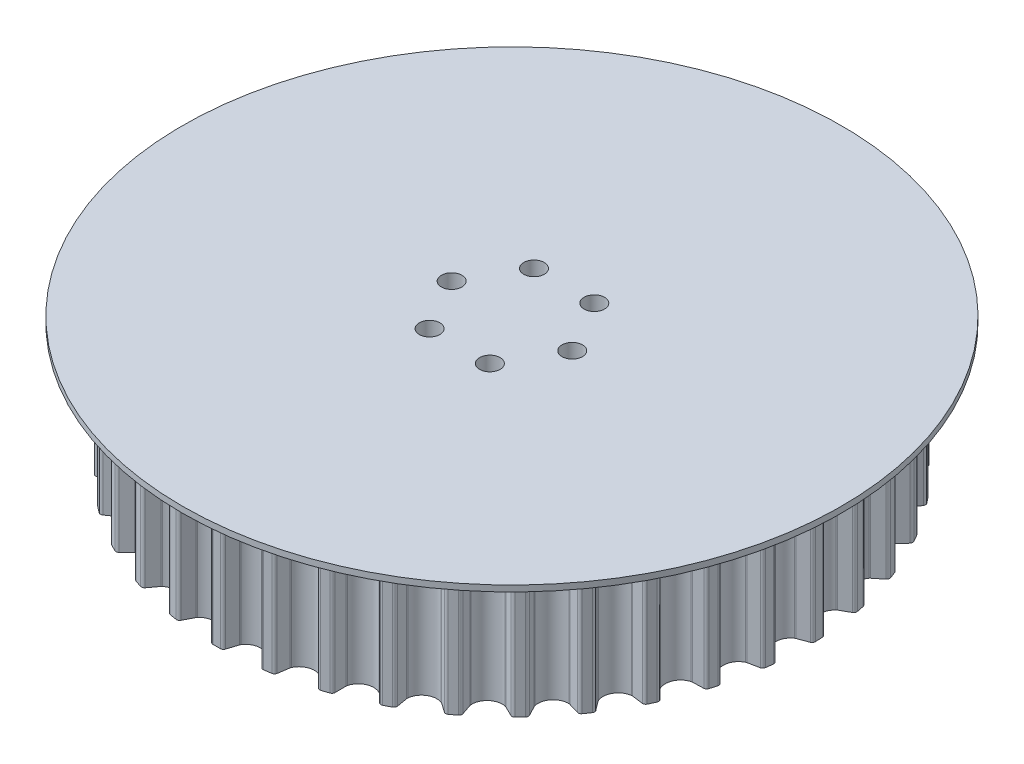
SolidWorks part; units mm, degrees
material "PETG"
ref_plane "Front Plane" through (0, 0, 0) normal (0, 0, 1) x (1, 0, 0)
ref_plane "Top Plane" through (0, 0, 0) normal (0, 1, 0) x (1, 0, 0)
ref_plane "Right Plane" through (0, 0, 0) normal (1, 0, 0) x (0, 0, -1)
sketch "Sketch7" plane through (0, 0, 0) normal (0, 1, 0) x (1, 0, 0)
  line L0 (0, 0) -> (0, 50000) construction
  line L1 (2.1092, 46.8388) -> (2.822, 48.5459)
  line L2 (0, 0) -> (3.9957, 49.4953) construction
  line L3 (0, 0) -> (-3.9957, 49.4953) construction
  line L4 (-2.1092, 46.8388) -> (-2.822, 48.5459)
  line L5 (9.5953, 45.8939) -> (10.5728, 47.4645)
  line L6 (5.4316, 46.5706) -> (5.0018, 48.3699)
  line L7 (16.833, 43.7604) -> (18.0497, 45.1539)
  line L8 (12.8317, 45.0962) -> (12.6961, 46.9412)
  line L9 (23.6346, 40.4935) -> (25.0591, 41.6738)
  line L10 (19.8995, 42.4539) -> (20.0616, 44.2967)
  line L11 (29.8242, 36.1779) -> (31.4196, 37.1143)
  line L12 (26.4519, 38.712) -> (26.9075, 40.5049)
  line L13 (35.2413, 30.9252) -> (36.9663, 31.5937)
  line L14 (32.3192, 33.9675) -> (33.0565, 35.6641)
  line L15 (39.7457, 24.8716) -> (41.5555, 25.2547)
  line L16 (37.3494, 28.3433) -> (38.3494, 29.8997)
  line L17 (43.2207, 18.1739) -> (45.0685, 18.2617)
  line L18 (41.4123, 21.985) -> (42.649, 23.3608)
  line L19 (45.5763, 11.0055) -> (47.4143, 10.7957)
  line L20 (44.4027, 15.0573) -> (45.844, 16.2169)
  line L21 (46.7515, 3.552) -> (48.5321, 3.0501)
  line L22 (46.243, 7.7396) -> (47.8518, 8.653)
  line L23 (46.7159, -3.9935) -> (48.3929, -4.7745)
  line L24 (46.8857, 0.2215) -> (48.6201, 0.865)
  line L25 (45.4703, -11.4355) -> (47.0003, -12.4754)
  line L26 (46.3141, -7.3024) -> (48.1293, -6.9454)
  line L27 (43.0471, -18.5814) -> (44.3905, -19.8532)
  line L28 (44.5429, -14.6371) -> (46.3919, -14.576)
  line L29 (39.509, -25.246) -> (40.6309, -26.7169)
  line L30 (41.6182, -21.5928) -> (43.4529, -21.829)
  line L31 (34.9476, -31.2567) -> (35.8191, -32.8885)
  line L32 (37.6155, -27.9892) -> (39.3886, -28.5167)
  line L33 (29.4811, -36.458) -> (30.0796, -38.2084)
  line L34 (32.6386, -33.6607) -> (34.3042, -34.4658)
  line L35 (23.2511, -40.7149) -> (23.561, -42.5387)
  line L36 (26.8164, -38.4604) -> (28.3312, -39.5222)
  line L37 (16.4188, -43.9174) -> (16.4322, -45.7673)
  line L38 (20.2996, -42.264) -> (21.6245, -43.5551)
  line L39 (9.1614, -45.9825) -> (8.8778, -47.8106)
  line L40 (13.2571, -44.973) -> (14.3578, -46.4599)
  line L41 (1.6666, -46.8566) -> (1.0935, -48.6155)
  line L42 (5.8713, -46.5172) -> (6.7192, -48.1614)
  line L43 (-5.8713, -46.5172) -> (-6.7192, -48.1614)
  line L44 (-1.6666, -46.8566) -> (-1.0935, -48.6155)
  line L45 (-13.2571, -44.973) -> (-14.3578, -46.4599)
  line L46 (-9.1614, -45.9825) -> (-8.8778, -47.8106)
  line L47 (-20.2996, -42.264) -> (-21.6245, -43.5551)
  line L48 (-16.4188, -43.9174) -> (-16.4322, -45.7673)
  line L49 (-26.8164, -38.4604) -> (-28.3312, -39.5222)
  line L50 (-23.2511, -40.7149) -> (-23.561, -42.5387)
  line L51 (-32.6386, -33.6607) -> (-34.3042, -34.4658)
  line L52 (-29.4811, -36.458) -> (-30.0796, -38.2084)
  line L53 (-37.6155, -27.9892) -> (-39.3886, -28.5167)
  line L54 (-34.9476, -31.2567) -> (-35.8191, -32.8885)
  line L55 (-41.6182, -21.5928) -> (-43.4529, -21.829)
  line L56 (-39.509, -25.246) -> (-40.6309, -26.7169)
  line L57 (-44.5429, -14.6371) -> (-46.3919, -14.576)
  line L58 (-43.0471, -18.5814) -> (-44.3905, -19.8532)
  line L59 (-46.3141, -7.3024) -> (-48.1293, -6.9454)
  line L60 (-45.4703, -11.4355) -> (-47.0003, -12.4754)
  line L61 (-46.8857, 0.2215) -> (-48.6201, 0.865)
  line L62 (-46.7159, -3.9935) -> (-48.3929, -4.7745)
  line L63 (0, 0) -> (2.0086, 46.666) construction
  line L64 (-46.243, 7.7396) -> (-47.8518, 8.653)
  line L65 (-46.7515, 3.552) -> (-48.5321, 3.0501)
  line L66 (-44.4027, 15.0573) -> (-45.844, 16.2169)
  line L67 (-45.5763, 11.0055) -> (-47.4143, 10.7957)
  line L68 (-41.4123, 21.985) -> (-42.649, 23.3608)
  line L69 (-43.2207, 18.1739) -> (-45.0685, 18.2617)
  line L70 (-37.3494, 28.3433) -> (-38.3494, 29.8997)
  line L71 (-39.7457, 24.8716) -> (-41.5555, 25.2547)
  line L72 (-32.3192, 33.9675) -> (-33.0565, 35.6641)
  line L73 (-35.2413, 30.9252) -> (-36.9663, 31.5937)
  line L74 (-26.4519, 38.712) -> (-26.9075, 40.5049)
  line L75 (-29.8242, 36.1779) -> (-31.4196, 37.1143)
  line L76 (-19.8995, 42.4539) -> (-20.0616, 44.2967)
  line L77 (-23.6346, 40.4935) -> (-25.0591, 41.6738)
  line L78 (-12.8317, 45.0962) -> (-12.6961, 46.9412)
  line L79 (-16.833, 43.7604) -> (-18.0497, 45.1539)
  line L80 (-5.4316, 46.5706) -> (-5.0018, 48.3699)
  line L81 (-9.5953, 45.8939) -> (-10.5728, 47.4645)
  circle A0 centre (0, 0) radius 49.6563 construction
  circle A1 centre (0, 0) radius 48.97 construction
  arc A2 (2.0086, 46.666) -> (-2.0086, 46.666) centre (0, 48.2207) cw
  arc A3 (2.0086, 46.666) -> (2.1092, 46.8388) centre (1.406, 47.1324) ccw
  arc A4 (2.822, 48.5459) -> (3.3253, 48.857) centre (3.2908, 48.3501) cw
  arc A5 (-2.822, 48.5459) -> (-3.3253, 48.857) centre (-3.2908, 48.3501) ccw
  arc A6 (-2.0086, 46.666) -> (-2.1092, 46.8388) centre (-1.406, 47.1324) cw
  arc A7 (3.3253, 48.857) -> (3.9404, 48.8112) centre (0, 0) cw
  arc A8 (-3.3253, 48.857) -> (-3.9404, 48.8112) centre (0, 0) ccw
  arc A9 (9.4683, 45.7395) -> (5.5032, 46.3839) centre (7.7351, 47.5963) cw
  arc A10 (9.4683, 45.7395) -> (9.5953, 45.8939) centre (8.9484, 46.2965) ccw
  arc A11 (10.5728, 47.4645) -> (11.1195, 47.6909) centre (11.0041, 47.1961) cw
  arc A12 (5.0018, 48.3699) -> (4.555, 48.7577) centre (4.5077, 48.2519) ccw
  arc A13 (5.5032, 46.3839) -> (5.4316, 46.5706) centre (6.1728, 46.7476) cw
  arc A14 (11.1195, 47.6909) -> (11.7193, 47.547) centre (0, 0) cw
  arc A15 (4.555, 48.7577) -> (3.9404, 48.8112) centre (0, 0) ccw
  arc A16 (16.6828, 43.6283) -> (12.8724, 44.9004) centre (15.27, 45.7391) cw
  arc A17 (16.6828, 43.6283) -> (16.833, 43.7604) centre (16.259, 44.2616) ccw
  arc A18 (18.0497, 45.1539) -> (18.6256, 45.2896) centre (18.4324, 44.8197) cw
  arc A19 (12.6961, 46.9412) -> (12.3173, 47.3956) centre (12.1895, 46.9039) ccw
  arc A20 (12.8724, 44.9004) -> (12.8317, 45.0962) centre (13.5917, 45.152) cw
  arc A21 (18.6256, 45.2896) -> (19.1946, 45.0514) centre (0, 0) cw
  arc A22 (12.3173, 47.3956) -> (11.7193, 47.547) centre (0, 0) ccw
  arc A23 (23.4653, 40.3872) -> (19.9082, 42.2541) centre (22.4093, 42.6973) cw
  arc A24 (23.4653, 40.3872) -> (23.6346, 40.4935) centre (23.1485, 41.0803) ccw
  arc A25 (25.0591, 41.6738) -> (25.6494, 41.7153) centre (25.3833, 41.2826) cw
  arc A26 (20.0616, 44.2967) -> (19.7605, 44.806) centre (19.5555, 44.3412) ccw
  arc A27 (19.9082, 42.2541) -> (19.8995, 42.4539) centre (20.6586, 42.3871) cw
  arc A28 (25.6494, 41.7153) -> (26.1728, 41.389) centre (0, 0) cw
  arc A29 (19.7605, 44.806) -> (19.1946, 45.0514) centre (0, 0) ccw
  arc A30 (29.64, 36.1001) -> (26.4285, 38.5134) centre (28.9682, 38.5497) cw
  arc A31 (29.64, 36.1001) -> (29.8242, 36.1779) centre (29.4384, 36.835) ccw
  arc A32 (31.4196, 37.1143) -> (32.0088, 37.0607) centre (31.6768, 36.6762) cw
  arc A33 (26.9075, 40.5049) -> (26.692, 41.056) centre (26.4151, 40.6301) ccw
  arc A34 (26.4285, 38.5134) -> (26.4519, 38.712) centre (27.1904, 38.5243) cw
  arc A35 (32.0088, 37.0607) -> (32.4731, 36.6546) centre (0, 0) cw
  arc A36 (26.692, 41.056) -> (26.1728, 41.389) centre (0, 0) ccw
  arc A37 (35.047, 30.8781) -> (32.2642, 33.7753) centre (34.7769, 33.4037) cw
  arc A38 (35.047, 30.8781) -> (35.2413, 30.9252) centre (34.966, 31.6357) ccw
  arc A39 (36.9663, 31.5937) -> (37.5393, 31.4462) centre (37.1498, 31.1199) cw
  arc A40 (33.0565, 35.6641) -> (32.9322, 36.2426) centre (32.5906, 35.8666) ccw
  arc A41 (32.2642, 33.7753) -> (32.3192, 33.9675) centre (33.018, 33.6638) cw
  arc A42 (37.5393, 31.4462) -> (37.9324, 30.9709) centre (0, 0) cw
  arc A43 (32.9322, 36.2426) -> (32.4731, 36.6546) centre (0, 0) ccw
  arc A44 (39.5464, 24.8563) -> (37.2643, 28.1623) centre (39.6849, 27.3925) cw
  arc A45 (39.5464, 24.8563) -> (39.7457, 24.8716) centre (39.5879, 25.6171) ccw
  arc A46 (41.5555, 25.2547) -> (42.0975, 25.0172) centre (41.6607, 24.7577) cw
  arc A47 (38.3494, 29.8997) -> (38.3195, 30.4906) centre (37.922, 30.1743) ccw
  arc A48 (37.2643, 28.1623) -> (37.3494, 28.3433) centre (37.9905, 27.9314) cw
  arc A49 (42.0975, 25.0172) -> (42.4093, 24.485) centre (0, 0) cw
  arc A50 (38.3195, 30.4906) -> (37.9324, 30.9709) centre (0, 0) ccw
  arc A51 (43.0215, 18.1907) -> (41.2993, 21.82) centre (43.565, 20.6719) cw
  arc A52 (43.0215, 18.1907) -> (43.2207, 18.1739) centre (43.1845, 18.935) ccw
  arc A53 (45.0685, 18.2617) -> (45.5654, 17.9404) centre (45.0927, 17.7542) cw
  arc A54 (42.649, 23.3608) -> (42.7143, 23.9489) centre (42.2712, 23.7004) ccw
  arc A55 (41.2993, 21.82) -> (41.4123, 21.985) centre (41.979, 21.4756) cw
  arc A56 (45.5654, 17.9404) -> (45.7877, 17.365) centre (0, 0) cw
  arc A57 (42.7143, 23.9489) -> (42.4093, 24.485) centre (0, 0) ccw
  arc A58 (45.3823, 11.054) -> (44.2647, 14.9126) centre (46.3169, 13.4158) cw
  arc A59 (45.3823, 11.054) -> (45.5763, 11.0055) centre (45.6627, 11.7626) ccw
  arc A60 (47.4143, 10.7957) -> (47.8532, 10.3988) centre (47.3567, 10.291) cw
  arc A61 (45.844, 16.2169) -> (46.0028, 16.7869) centre (45.5256, 16.6127) ccw
  arc A62 (44.2647, 14.9126) -> (44.4027, 15.0573) centre (44.8803, 14.4636) cw
  arc A63 (47.8532, 10.3988) -> (47.9803, 9.7953) centre (0, 0) cw
  arc A64 (46.0028, 16.7869) -> (45.7877, 17.365) centre (0, 0) ccw
  arc A65 (46.5678, 3.631) -> (46.0836, 7.6189) centre (47.8691, 5.8124) cw
  arc A66 (46.5678, 3.631) -> (46.7515, 3.552) centre (46.9582, 4.2854) ccw
  arc A67 (48.5321, 3.0501) -> (48.9016, 2.588) centre (48.3942, 2.5611) cw
  arc A68 (47.8518, 8.653) -> (48.0999, 9.1901) centre (47.6009, 9.0948) ccw
  arc A69 (46.0836, 7.6189) -> (46.243, 7.7396) centre (46.6193, 7.0769) cw
  arc A70 (48.9016, 2.588) -> (48.9303, 1.9718) centre (0, 0) cw
  arc A71 (48.0999, 9.1901) -> (47.9803, 9.7953) centre (0, 0) ccw
  arc A72 (46.5473, -3.886) -> (46.709, 0.1279) centre (48.1816, -1.9417) cw
  arc A73 (46.5473, -3.886) -> (46.7159, -3.9935) centre (47.0376, -3.3027) ccw
  arc A74 (48.3929, -4.7745) -> (48.6834, -5.2899) centre (48.1784, -5.235) cw
  arc A75 (48.6201, 0.865) -> (48.9512, 1.3553) centre (48.4434, 1.3413) ccw
  arc A76 (46.709, 0.1279) -> (46.8857, 0.2215) centre (47.1508, -0.493) cw
  arc A77 (48.6834, -5.2899) -> (48.613, -5.9027) centre (0, 0) cw
  arc A78 (48.9512, 1.3553) -> (48.9303, 1.9718) centre (0, 0) ccw
  arc A79 (45.3211, -11.3024) -> (46.1247, -7.3664) centre (47.2462, -9.6454) cw
  arc A80 (45.3211, -11.3024) -> (45.4703, -11.4355) centre (45.8986, -10.8053) ccw
  arc A81 (47.0003, -12.4754) -> (47.2045, -13.0308) centre (46.7147, -12.8956) cw
  arc A82 (48.1293, -6.9454) -> (48.5347, -6.5145) centre (48.0312, -6.447) ccw
  arc A83 (46.1247, -7.3664) -> (46.3141, -7.3024) centre (46.4611, -8.0501) cw
  arc A84 (47.2045, -13.0308) -> (47.0366, -13.6243) centre (0, 0) cw
  arc A85 (48.5347, -6.5145) -> (48.613, -5.9027) centre (0, 0) ccw
  arc A86 (42.9212, -18.426) -> (44.3457, -14.6699) centre (45.0871, -17.0993) cw
  arc A87 (42.9212, -18.426) -> (43.0471, -18.5814) centre (43.571, -18.028) ccw
  arc A88 (44.3905, -19.8532) -> (44.5029, -20.4341) centre (44.0412, -20.2221) cw
  arc A89 (46.3919, -14.576) -> (46.8612, -14.2157) centre (46.3751, -14.0682) ccw
  arc A90 (44.3457, -14.6699) -> (44.5429, -14.6371) centre (44.5681, -15.3987) cw
  arc A91 (44.5029, -20.4341) -> (44.242, -20.9931) centre (0, 0) cw
  arc A92 (46.8612, -14.2157) -> (47.0366, -13.6243) centre (0, 0) ccw
  arc A93 (39.4096, -25.0725) -> (41.4182, -21.5935) centre (41.7604, -24.1103) cw
  arc A94 (39.4096, -25.0725) -> (39.509, -25.246) centre (40.1148, -24.7838) ccw
  arc A95 (40.6309, -26.7169) -> (40.6487, -27.3083) centre (40.227, -27.025) cw
  arc A96 (43.4529, -21.829) -> (43.974, -21.5487) centre (43.5178, -21.3251) ccw
  arc A97 (41.4182, -21.5935) -> (41.6182, -21.5928) centre (41.5209, -22.3486) cw
  arc A98 (40.6487, -27.3083) -> (40.3015, -27.8181) centre (0, 0) cw
  arc A99 (43.974, -21.5487) -> (44.242, -20.9931) centre (0, 0) ccw
  arc A100 (34.8774, -31.0695) -> (37.418, -27.9578) centre (37.352, -30.497) cw
  arc A101 (34.8774, -31.0695) -> (34.9476, -31.2567) centre (35.6198, -30.8978) ccw
  arc A102 (35.8191, -32.8885) -> (35.7418, -33.4752) centre (35.371, -33.1279) cw
  arc A103 (39.3886, -28.5167) -> (39.9479, -28.3236) centre (39.5335, -28.0297) ccw
  arc A104 (37.418, -27.9578) -> (37.6155, -27.9892) centre (37.3982, -28.7196) cw
  arc A105 (35.7418, -33.4752) -> (35.3173, -33.9227) centre (0, 0) cw
  arc A106 (39.9479, -28.3236) -> (40.3015, -27.8181) centre (0, 0) ccw
  arc A107 (29.4418, -36.2619) -> (32.4487, -33.598) centre (31.9762, -36.0937) cw
  arc A108 (29.4418, -36.2619) -> (29.4811, -36.458) centre (30.2021, -36.2115) ccw
  arc A109 (30.0796, -38.2084) -> (29.9091, -38.7751) centre (29.5988, -38.3728) cw
  arc A110 (34.3042, -34.4658) -> (34.8872, -34.3649) centre (34.5253, -34.0084) ccw
  arc A111 (32.4487, -33.598) -> (32.6386, -33.6607) centre (32.307, -34.3467) cw
  arc A112 (29.9091, -38.7751) -> (29.4183, -39.1487) centre (0, 0) cw
  arc A113 (34.8872, -34.3649) -> (35.3173, -33.9227) centre (0, 0) ccw
  arc A114 (23.2437, -40.5151) -> (26.639, -38.3681) centre (25.7723, -40.7557) cw
  arc A115 (23.2437, -40.5151) -> (23.2511, -40.7149) centre (24.0023, -40.5873) ccw
  arc A116 (23.561, -42.5387) -> (23.3019, -43.0707) centre (23.0601, -42.6238) cw
  arc A117 (28.3312, -39.5222) -> (28.9229, -39.5162) centre (28.6228, -39.1062) ccw
  arc A118 (26.639, -38.3681) -> (26.8164, -38.4604) centre (26.379, -39.0844) cw
  arc A119 (23.3019, -43.0707) -> (22.7575, -43.3608) centre (0, 0) cw
  arc A120 (28.9229, -39.5162) -> (29.4183, -39.1487) centre (0, 0) ccw
  arc A121 (16.4436, -43.719) -> (20.1394, -42.1444) centre (18.9009, -44.3621) cw
  arc A122 (16.4436, -43.719) -> (16.4188, -43.9174) centre (17.1808, -43.9119) ccw
  arc A123 (16.4322, -45.7673) -> (16.0911, -46.2508) centre (15.9241, -45.771) cw
  arc A124 (21.6245, -43.5551) -> (22.2095, -43.644) centre (21.9791, -43.1912) ccw
  arc A125 (20.1394, -42.1444) -> (20.2996, -42.264) centre (19.7678, -42.8097) cw
  arc A126 (16.0911, -46.2508) -> (15.5072, -46.4498) centre (0, 0) cw
  arc A127 (22.2095, -43.644) -> (22.7575, -43.3608) centre (0, 0) ccw
  arc A128 (9.2177, -45.7906) -> (13.1181, -44.8293) centre (11.54, -46.8195) cw
  arc A129 (9.2177, -45.7906) -> (9.1614, -45.9825) centre (9.9144, -46.0993) ccw
  arc A130 (8.8778, -47.8106) -> (8.4636, -48.2331) centre (8.3757, -47.7327) cw
  arc A131 (14.3578, -46.4599) -> (14.9209, -46.6415) centre (14.7661, -46.1576) ccw
  arc A132 (13.1181, -44.8293) -> (13.2571, -44.973) centre (12.6447, -45.4263) cw
  arc A133 (8.4636, -48.2331) -> (7.8553, -48.3359) centre (0, 0) cw
  arc A134 (14.9209, -46.6415) -> (15.5072, -46.4498) centre (0, 0) ccw
  arc A135 (1.753, -46.6763) -> (5.7571, -46.353) centre (3.8802, -48.0643) cw
  arc A136 (1.753, -46.6763) -> (1.6666, -46.8566) centre (2.3911, -47.0927) ccw
  arc A137 (1.0935, -48.6155) -> (0.6168, -48.9661) centre (0.6104, -48.4581) cw
  arc A138 (6.7192, -48.1614) -> (7.2459, -48.431) centre (7.1707, -47.9285) ccw
  arc A139 (5.7571, -46.353) -> (5.8713, -46.5172) centre (5.194, -46.8664) cw
  arc A140 (0.6168, -48.9661) -> (0, -48.97) centre (0, 0) cw
  arc A141 (7.2459, -48.431) -> (7.8553, -48.3359) centre (0, 0) ccw
  arc A142 (-5.7571, -46.353) -> (-1.753, -46.6763) centre (-3.8802, -48.0643) cw
  arc A143 (-5.7571, -46.353) -> (-5.8713, -46.5172) centre (-5.194, -46.8664) ccw
  arc A144 (-6.7192, -48.1614) -> (-7.2459, -48.431) centre (-7.1707, -47.9285) cw
  arc A145 (-1.0935, -48.6155) -> (-0.6168, -48.9661) centre (-0.6104, -48.4581) ccw
  arc A146 (-1.753, -46.6763) -> (-1.6666, -46.8566) centre (-2.3911, -47.0927) cw
  arc A147 (-7.2459, -48.431) -> (-7.8553, -48.3359) centre (0, 0) cw
  arc A148 (-0.6168, -48.9661) -> (0, -48.97) centre (0, 0) ccw
  arc A149 (-13.1181, -44.8293) -> (-9.2177, -45.7906) centre (-11.54, -46.8195) cw
  arc A150 (-13.1181, -44.8293) -> (-13.2571, -44.973) centre (-12.6447, -45.4263) ccw
  arc A151 (-14.3578, -46.4599) -> (-14.9209, -46.6415) centre (-14.7661, -46.1576) cw
  arc A152 (-8.8778, -47.8106) -> (-8.4636, -48.2331) centre (-8.3757, -47.7327) ccw
  arc A153 (-9.2177, -45.7906) -> (-9.1614, -45.9825) centre (-9.9144, -46.0993) cw
  arc A154 (-14.9209, -46.6415) -> (-15.5072, -46.4498) centre (0, 0) cw
  arc A155 (-8.4636, -48.2331) -> (-7.8553, -48.3359) centre (0, 0) ccw
  arc A156 (-20.1394, -42.1444) -> (-16.4436, -43.719) centre (-18.9009, -44.3621) cw
  arc A157 (-20.1394, -42.1444) -> (-20.2996, -42.264) centre (-19.7678, -42.8097) ccw
  arc A158 (-21.6245, -43.5551) -> (-22.2095, -43.644) centre (-21.9791, -43.1912) cw
  arc A159 (-16.4322, -45.7673) -> (-16.0911, -46.2508) centre (-15.9241, -45.771) ccw
  arc A160 (-16.4436, -43.719) -> (-16.4188, -43.9174) centre (-17.1808, -43.9119) cw
  arc A161 (-22.2095, -43.644) -> (-22.7575, -43.3608) centre (0, 0) cw
  arc A162 (-16.0911, -46.2508) -> (-15.5072, -46.4498) centre (0, 0) ccw
  arc A163 (-26.639, -38.3681) -> (-23.2437, -40.5151) centre (-25.7723, -40.7557) cw
  arc A164 (-26.639, -38.3681) -> (-26.8164, -38.4604) centre (-26.379, -39.0844) ccw
  arc A165 (-28.3312, -39.5222) -> (-28.9229, -39.5162) centre (-28.6228, -39.1062) cw
  arc A166 (-23.561, -42.5387) -> (-23.3019, -43.0707) centre (-23.0601, -42.6238) ccw
  arc A167 (-23.2437, -40.5151) -> (-23.2511, -40.7149) centre (-24.0023, -40.5873) cw
  arc A168 (-28.9229, -39.5162) -> (-29.4183, -39.1487) centre (0, 0) cw
  arc A169 (-23.3019, -43.0707) -> (-22.7575, -43.3608) centre (0, 0) ccw
  arc A170 (-32.4487, -33.598) -> (-29.4418, -36.2619) centre (-31.9762, -36.0937) cw
  arc A171 (-32.4487, -33.598) -> (-32.6386, -33.6607) centre (-32.307, -34.3467) ccw
  arc A172 (-34.3042, -34.4658) -> (-34.8872, -34.3649) centre (-34.5253, -34.0084) cw
  arc A173 (-30.0796, -38.2084) -> (-29.9091, -38.7751) centre (-29.5988, -38.3728) ccw
  arc A174 (-29.4418, -36.2619) -> (-29.4811, -36.458) centre (-30.2021, -36.2115) cw
  arc A175 (-34.8872, -34.3649) -> (-35.3173, -33.9227) centre (0, 0) cw
  arc A176 (-29.9091, -38.7751) -> (-29.4183, -39.1487) centre (0, 0) ccw
  arc A177 (-37.418, -27.9578) -> (-34.8774, -31.0695) centre (-37.352, -30.497) cw
  arc A178 (-37.418, -27.9578) -> (-37.6155, -27.9892) centre (-37.3982, -28.7196) ccw
  arc A179 (-39.3886, -28.5167) -> (-39.9479, -28.3236) centre (-39.5335, -28.0297) cw
  arc A180 (-35.8191, -32.8885) -> (-35.7418, -33.4752) centre (-35.371, -33.1279) ccw
  arc A181 (-34.8774, -31.0695) -> (-34.9476, -31.2567) centre (-35.6198, -30.8978) cw
  arc A182 (-39.9479, -28.3236) -> (-40.3015, -27.8181) centre (0, 0) cw
  arc A183 (-35.7418, -33.4752) -> (-35.3173, -33.9227) centre (0, 0) ccw
  arc A184 (-41.4182, -21.5935) -> (-39.4096, -25.0725) centre (-41.7604, -24.1104) cw
  arc A185 (-41.4182, -21.5935) -> (-41.6182, -21.5928) centre (-41.5209, -22.3486) ccw
  arc A186 (-43.4529, -21.829) -> (-43.974, -21.5487) centre (-43.5178, -21.3251) cw
  arc A187 (-40.6309, -26.7169) -> (-40.6487, -27.3083) centre (-40.227, -27.025) ccw
  arc A188 (-39.4096, -25.0725) -> (-39.509, -25.246) centre (-40.1148, -24.7838) cw
  arc A189 (-43.974, -21.5487) -> (-44.242, -20.9931) centre (0, 0) cw
  arc A190 (-40.6487, -27.3083) -> (-40.3015, -27.8181) centre (0, 0) ccw
  arc A191 (-44.3457, -14.6699) -> (-42.9212, -18.426) centre (-45.0871, -17.0993) cw
  arc A192 (-44.3457, -14.6699) -> (-44.5429, -14.6371) centre (-44.5681, -15.3987) ccw
  arc A193 (-46.3919, -14.576) -> (-46.8612, -14.2157) centre (-46.3751, -14.0682) cw
  arc A194 (-44.3905, -19.8532) -> (-44.5029, -20.4341) centre (-44.0412, -20.2221) ccw
  arc A195 (-42.9212, -18.426) -> (-43.0471, -18.5814) centre (-43.571, -18.028) cw
  arc A196 (-46.8612, -14.2157) -> (-47.0366, -13.6243) centre (0, 0) cw
  arc A197 (-44.5029, -20.4341) -> (-44.242, -20.9931) centre (0, 0) ccw
  arc A198 (-46.1247, -7.3664) -> (-45.3211, -11.3024) centre (-47.2462, -9.6454) cw
  arc A199 (-46.1247, -7.3664) -> (-46.3141, -7.3024) centre (-46.4611, -8.0501) ccw
  arc A200 (-48.1293, -6.9454) -> (-48.5347, -6.5145) centre (-48.0312, -6.447) cw
  arc A201 (-47.0003, -12.4754) -> (-47.2045, -13.0308) centre (-46.7147, -12.8956) ccw
  arc A202 (-45.3211, -11.3024) -> (-45.4703, -11.4355) centre (-45.8986, -10.8053) cw
  arc A203 (-48.5347, -6.5145) -> (-48.613, -5.9027) centre (0, 0) cw
  arc A204 (-47.2045, -13.0308) -> (-47.0366, -13.6243) centre (0, 0) ccw
  arc A205 (-46.709, 0.1279) -> (-46.5473, -3.886) centre (-48.1816, -1.9417) cw
  arc A206 (-46.709, 0.1279) -> (-46.8857, 0.2215) centre (-47.1508, -0.493) ccw
  arc A207 (-48.6201, 0.865) -> (-48.9512, 1.3553) centre (-48.4434, 1.3413) cw
  arc A208 (-48.3929, -4.7745) -> (-48.6834, -5.2899) centre (-48.1784, -5.235) ccw
  arc A209 (-46.5473, -3.886) -> (-46.7159, -3.9935) centre (-47.0376, -3.3027) cw
  arc A210 (-48.9512, 1.3553) -> (-48.9303, 1.9718) centre (0, 0) cw
  arc A211 (-48.6834, -5.2899) -> (-48.613, -5.9027) centre (0, 0) ccw
  arc A212 (-46.0836, 7.6189) -> (-46.5678, 3.631) centre (-47.8691, 5.8124) cw
  arc A213 (-46.0836, 7.6189) -> (-46.243, 7.7396) centre (-46.6193, 7.0769) ccw
  arc A214 (-47.8518, 8.653) -> (-48.0999, 9.1901) centre (-47.6009, 9.0948) cw
  arc A215 (-48.5321, 3.0501) -> (-48.9016, 2.588) centre (-48.3942, 2.5611) ccw
  arc A216 (-46.5678, 3.631) -> (-46.7515, 3.552) centre (-46.9582, 4.2854) cw
  arc A217 (-48.0999, 9.1901) -> (-47.9803, 9.7953) centre (0, 0) cw
  arc A218 (-48.9016, 2.588) -> (-48.9303, 1.9718) centre (0, 0) ccw
  arc A219 (-44.2647, 14.9126) -> (-45.3823, 11.054) centre (-46.3169, 13.4158) cw
  arc A220 (-44.2647, 14.9126) -> (-44.4027, 15.0573) centre (-44.8803, 14.4636) ccw
  arc A221 (-45.844, 16.2169) -> (-46.0028, 16.7869) centre (-45.5256, 16.6127) cw
  arc A222 (-47.4143, 10.7957) -> (-47.8532, 10.3988) centre (-47.3567, 10.291) ccw
  arc A223 (-45.3823, 11.054) -> (-45.5763, 11.0055) centre (-45.6627, 11.7626) cw
  arc A224 (-46.0028, 16.7869) -> (-45.7877, 17.365) centre (0, 0) cw
  arc A225 (-47.8532, 10.3988) -> (-47.9803, 9.7953) centre (0, 0) ccw
  arc A226 (-41.2993, 21.82) -> (-43.0215, 18.1907) centre (-43.565, 20.6719) cw
  arc A227 (-41.2993, 21.82) -> (-41.4123, 21.985) centre (-41.979, 21.4756) ccw
  arc A228 (-42.649, 23.3608) -> (-42.7143, 23.9489) centre (-42.2712, 23.7004) cw
  arc A229 (-45.0685, 18.2617) -> (-45.5654, 17.9404) centre (-45.0927, 17.7542) ccw
  arc A230 (-43.0215, 18.1907) -> (-43.2207, 18.1739) centre (-43.1845, 18.935) cw
  arc A231 (-42.7143, 23.9489) -> (-42.4093, 24.485) centre (0, 0) cw
  arc A232 (-45.5654, 17.9404) -> (-45.7877, 17.365) centre (0, 0) ccw
  arc A233 (-37.2643, 28.1623) -> (-39.5464, 24.8563) centre (-39.6849, 27.3925) cw
  arc A234 (-37.2643, 28.1623) -> (-37.3494, 28.3433) centre (-37.9905, 27.9314) ccw
  arc A235 (-38.3494, 29.8997) -> (-38.3195, 30.4906) centre (-37.922, 30.1743) cw
  arc A236 (-41.5555, 25.2547) -> (-42.0975, 25.0172) centre (-41.6607, 24.7577) ccw
  arc A237 (-39.5464, 24.8563) -> (-39.7457, 24.8716) centre (-39.5879, 25.6171) cw
  arc A238 (-38.3195, 30.4906) -> (-37.9324, 30.9709) centre (0, 0) cw
  arc A239 (-42.0975, 25.0172) -> (-42.4093, 24.485) centre (0, 0) ccw
  arc A240 (-32.2642, 33.7753) -> (-35.047, 30.8781) centre (-34.7769, 33.4037) cw
  arc A241 (-32.2642, 33.7753) -> (-32.3192, 33.9675) centre (-33.018, 33.6638) ccw
  arc A242 (-33.0565, 35.6641) -> (-32.9322, 36.2426) centre (-32.5906, 35.8666) cw
  arc A243 (-36.9663, 31.5937) -> (-37.5393, 31.4462) centre (-37.1498, 31.1199) ccw
  arc A244 (-35.047, 30.8781) -> (-35.2413, 30.9252) centre (-34.966, 31.6357) cw
  arc A245 (-32.9322, 36.2426) -> (-32.4731, 36.6546) centre (0, 0) cw
  arc A246 (-37.5393, 31.4462) -> (-37.9324, 30.9709) centre (0, 0) ccw
  arc A247 (-26.4285, 38.5134) -> (-29.64, 36.1001) centre (-28.9682, 38.5497) cw
  arc A248 (-26.4285, 38.5134) -> (-26.4519, 38.712) centre (-27.1904, 38.5243) ccw
  arc A249 (-26.9075, 40.5049) -> (-26.692, 41.056) centre (-26.4151, 40.6301) cw
  arc A250 (-31.4196, 37.1143) -> (-32.0088, 37.0607) centre (-31.6768, 36.6762) ccw
  arc A251 (-29.64, 36.1001) -> (-29.8242, 36.1779) centre (-29.4384, 36.835) cw
  arc A252 (-26.692, 41.056) -> (-26.1728, 41.389) centre (0, 0) cw
  arc A253 (-32.0088, 37.0607) -> (-32.4731, 36.6546) centre (0, 0) ccw
  arc A254 (-19.9082, 42.2541) -> (-23.4653, 40.3872) centre (-22.4093, 42.6973) cw
  arc A255 (-19.9082, 42.2541) -> (-19.8995, 42.4539) centre (-20.6586, 42.3871) ccw
  arc A256 (-20.0616, 44.2967) -> (-19.7605, 44.806) centre (-19.5555, 44.3412) cw
  arc A257 (-25.0591, 41.6738) -> (-25.6494, 41.7153) centre (-25.3833, 41.2826) ccw
  arc A258 (-23.4653, 40.3872) -> (-23.6346, 40.4935) centre (-23.1485, 41.0803) cw
  arc A259 (-19.7605, 44.806) -> (-19.1946, 45.0514) centre (0, 0) cw
  arc A260 (-25.6494, 41.7153) -> (-26.1728, 41.389) centre (0, 0) ccw
  arc A261 (-12.8724, 44.9004) -> (-16.6828, 43.6283) centre (-15.27, 45.7391) cw
  arc A262 (-12.8724, 44.9004) -> (-12.8317, 45.0962) centre (-13.5917, 45.152) ccw
  arc A263 (-12.6961, 46.9412) -> (-12.3173, 47.3956) centre (-12.1895, 46.9039) cw
  arc A264 (-18.0497, 45.1539) -> (-18.6256, 45.2896) centre (-18.4324, 44.8197) ccw
  arc A265 (-16.6828, 43.6283) -> (-16.833, 43.7604) centre (-16.259, 44.2616) cw
  arc A266 (-12.3173, 47.3956) -> (-11.7193, 47.547) centre (0, 0) cw
  arc A267 (-18.6256, 45.2896) -> (-19.1946, 45.0514) centre (0, 0) ccw
  arc A268 (-5.5032, 46.3839) -> (-9.4683, 45.7395) centre (-7.7351, 47.5963) cw
  arc A269 (-5.5032, 46.3839) -> (-5.4316, 46.5706) centre (-6.1728, 46.7476) ccw
  arc A270 (-5.0018, 48.3699) -> (-4.555, 48.7577) centre (-4.5077, 48.2519) cw
  arc A271 (-10.5728, 47.4645) -> (-11.1195, 47.6909) centre (-11.0041, 47.1961) ccw
  arc A272 (-9.4683, 45.7395) -> (-9.5953, 45.8939) centre (-8.9484, 46.2965) cw
  arc A273 (-4.555, 48.7577) -> (-3.9404, 48.8112) centre (0, 0) cw
  arc A274 (-11.1195, 47.6909) -> (-11.7193, 47.547) centre (0, 0) ccw
  point P14 (0, 48.97)
  dimension "D1" = 99.3127
  dimension "D2" = 97.94
  dimension "D3" = 2.54
  dimension "D5" = 0.762
  dimension "D6" = 0.508
  dimension "D4" = 22.664
  dimension "D7" = 0.7493
  dimension "D9" = 4.0172
  dimension "D8" = 8
  dimension "D10" = 39
extrude "Boss-Extrude5" add sketch "Sketch7" along normal mid plane 22 contours A271 A274 A266 A263 L78 A262 A261 A265 L79 A264 A267 A259 A256 L76 A255 A254 A258 L77 A257 A260 A252 A249 L74 A248 A247 A251 L75 A250 A253 A245 A242 L72 A241 A240 A244 L73 A243 A246 A238 A235 L70 A234 A233 A237 L71 A236 A239 A231 A228 L68 A227 region at (0, 0, 0)
sketch "Sketch2" plane through (0, 11, 0) normal (0, 1, 0) x (1, 0, 0)
  circle A0 centre (0, 0) radius 54.6563
  dimension "D1" = 109.3127
extrude "Boss-Extrude2" add sketch "Sketch2" along normal blind 1
sketch "Sketch3" plane through (0, 12, 0) normal (0, 1, 0) x (1, 0, 0)
  line L0 (0, 0) -> (10, 0) construction
  circle A0 centre (10, 0) radius 1.7
  circle A1 centre (5, -8.6603) radius 1.7
  circle A2 centre (-5, -8.6603) radius 1.7
  circle A3 centre (-10, 0) radius 1.7
  circle A4 centre (-5, 8.6603) radius 1.7
  circle A5 centre (5, 8.6603) radius 1.7
  dimension "D1" = 10
  dimension "D2" = 3.4
  dimension "D3" = 6
extrude "Cut-Extrude1" cut sketch "Sketch3" against normal through all
sketch "Sketch4" plane through (0, -11, 0) normal (0, 1, 0) x (1, 0, 0)
  line L0 (0, 0) -> (5, -8.6603) construction
  circle A0 centre (5, -8.6603) radius 3
  circle A1 centre (-5, -8.6603) radius 3
  circle A2 centre (-10, 0) radius 3
  circle A3 centre (-5, 8.6603) radius 3
  circle A4 centre (5, 8.6603) radius 3
  circle A5 centre (10, 0) radius 3
  dimension "D1" = 6
  dimension "D2" = 6
extrude "Cut-Extrude2" cut sketch "Sketch4" along normal offset from surface (13 mm away) 10 up to face at (10, 12, 1.7)
sketch "Sketch6" plane through (0, -11, 0) normal (0, -1, 0) x (1, 0, 0)
  line L0 (0, 0) -> (35, 0) construction
  circle A0 centre (35, 0) radius 1.985
  circle A1 centre (-17.5, -30.3109) radius 1.985
  circle A2 centre (-17.5, 30.3109) radius 1.985
  dimension "D2" = 3.97
  dimension "D1" = 35
extrude "Cut-Extrude3" cut sketch "Sketch6" against normal blind 20
equation "\"pitch\"= 8mm"
equation "\"n\"= 39"
equation "\"pitch_dia\"= \"pitch\" * \"n\" / PI"
equation "\"outside_dia\"= 97.94'From manual. For 39 teeth"
equation "\"belt_width\"= 22mm"
equation "\"D1@Sketch2\"=\"pitch_dia\"+10.00mm"
equation "\"tol_dia_id_intfc\" = 0.0200mm ' For hole diameters - Interference fit"
equation "\"tol_dia_id_slip\"  = 0.0300mm ' For hole diameters - Slip fit"
equation "\"tol_dia_id_clear\" = 0.0500mm ' For hole diameters - Clearance fit"
equation "\"tol_dia_od_intfc\" = 0.0200mm ' For shaft diameters - Interference fit"
equation "\"tol_dia_od_slip\"  = 0.0300mm ' For shaft diameters - Slip fit"
equation "\"tol_dia_od_clear\" = 0.0500mm ' For shaft diameters - Clearance fit"
equation "\"tol_general_intfc\"= 0.0030mm ' For general parts (Horiz) - Interference fit"
equation "\"tol_general_slip\" = 0.0050mm ' For general parts (Horiz) - Slip fit"
equation "\"tol_general_clear\"= 0.0100mm ' For general parts (Horiz) - Clearance fit"
equation "\"tol_layer_intfc\"  = 0.0030mm ' For all parts (Vert) - Interference fit"
equation "\"tol_layer_slip\"   = 0.0050mm ' For all parts (Vert) - Slip fit"
equation "\"tol_layer_clear\"  = 0.0100mm ' For all parts (Vert) - Clearance fit"
equation "\"tol_corner_rad\"   = 0.100mm ' For corners that fit into other parts"
equation "\"D2@Sketch6\"=3.95+\"tol_dia_id_intfc\""
equation "\"D1@Sketch7\"=\"pitch_dia\""
equation "\"D2@Sketch7\"=\"outside_dia\""
equation "\"D8@Sketch7\"=\"pitch\""
equation "\"D10@Sketch7\"=\"n\""
equation "\"D1@Boss-Extrude5\"= \"belt_width\""
